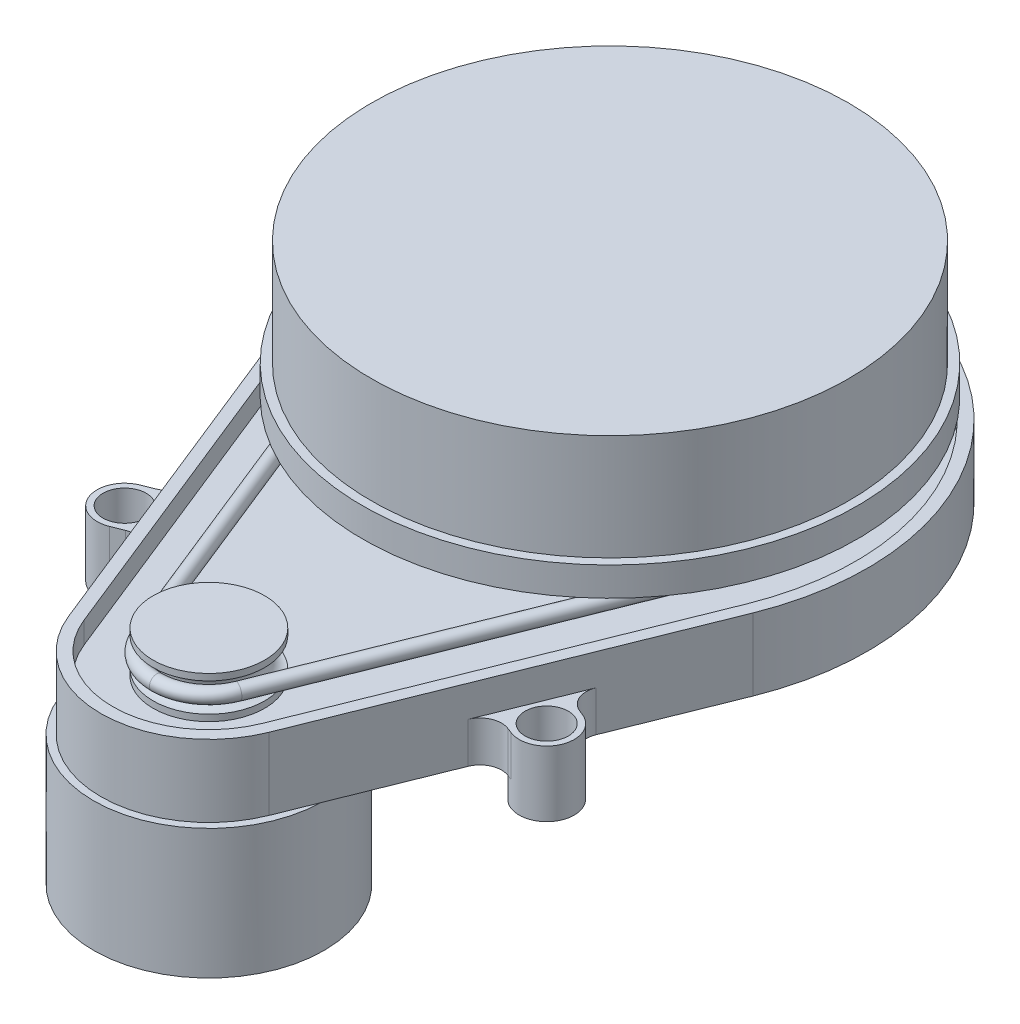
SolidWorks part; units mm, degrees
ref_plane "前基準面" through (0, 0, 0) normal (0, 0, 1) x (1, 0, 0)
ref_plane "上基準面" through (0, 0, 0) normal (0, 1, 0) x (1, 0, 0)
ref_plane "右基準面" through (0, 0, 0) normal (1, 0, 0) x (0, 0, -1)
sketch "草圖1" plane through (0, 0, 0) normal (0, 1, 0) x (1, 0, 0)
  line L0 (0, 0) -> (0, 50000) construction
  line L1 (0, 0) -> (50000, 0) construction
  line L2 (0, 39.9) -> (-5.4, 39.9)
  line L3 (0, -36.6) -> (27.81, -36.6)
  line L4 (0, -39.7) -> (-27.7, -39.7)
  line L5 (33.1767, -13.318) -> (13.9203, -61.288)
  line L6 (-33.1767, -13.318) -> (-13.9203, -61.288)
  circle A0 centre (0, 0) radius 35.75
  circle A1 centre (0, -55.7) radius 15
  point P14 (0, -70.7)
  dimension "D1" = 71.5
  dimension "D9" = 30
  dimension "D2" = 5.4
  dimension "D3" = 39.9
  dimension "D4" = 27.81
  dimension "D5" = 27.7
  dimension "D6" = 76.5
  dimension "D7" = 110.6
  dimension "D8" = 79.6
sketch "草圖2" plane through (0, 0, 0) normal (0, 1, 0) x (1, 0, 0)
  line L0 (-33.1767, -13.318) -> (-13.9203, -61.288) construction
  line L1 (33.1767, -13.318) -> (13.9203, -61.288) construction
  line L2 (-33.1767, -13.318) -> (-13.9203, -61.288)
  line L3 (33.1767, -13.318) -> (13.9203, -61.288)
  circle A0 centre (0, -55.7) radius 15 construction
  circle A1 centre (0, 0) radius 35.75 construction
  arc A2 (-13.9203, -61.288) -> (13.9203, -61.288) centre (0, -55.7) ccw
  arc A3 (33.1767, -13.318) -> (-33.1767, -13.318) centre (0, 0) ccw
extrude "填料-伸長1" add sketch "草圖2" along normal blind 10
sketch "草圖3" plane through (0, 10, 0) normal (0, 1, 0) x (1, 0, 0)
  line L22 (12.3891, -60.6733) -> (31.6455, -12.7033)
  line L23 (-31.6455, -12.7033) -> (-12.3891, -60.6733)
  line L24 (-33.1767, -13.318) -> (-13.9203, -61.288)
  line L25 (13.9203, -61.288) -> (33.1767, -13.318)
  line L26 (-33.1767, -13.318) -> (-13.9203, -61.288)
  line L27 (13.9203, -61.288) -> (33.1767, -13.318)
  arc A20 (31.6455, -12.7033) -> (-31.6455, -12.7033) centre (0, 0) ccw
  arc A21 (-12.3891, -60.6733) -> (12.3891, -60.6733) centre (0, -55.7) ccw
  arc A22 (33.1767, -13.318) -> (-33.1767, -13.318) centre (0, 0) ccw
  arc A23 (-13.9203, -61.288) -> (13.9203, -61.288) centre (0, -55.7) ccw
  arc A24 (33.1767, -13.318) -> (-33.1767, -13.318) centre (0, 0) ccw
  arc A25 (-13.9203, -61.288) -> (13.9203, -61.288) centre (0, -55.7) ccw
  dimension "D1" = 0
  dimension "D2" = 1.65
extrude "除料-伸長1" cut sketch "草圖3" against normal blind 3 contours L23 A21 L22 A20 region at (0, 10, 11.8793)
sketch "草圖4" plane through (0, 7, 0) normal (0, 1, 0) x (1, 0, 0)
  circle A0 centre (0, -55.7) radius 7.75
  dimension "D1" = 15.5
extrude "填料-伸長2" add sketch "草圖4" along normal blind 5.8
sketch "草圖5" plane through (0, 0, 0) normal (1, 0, 0) x (0, 0, -1)
  line L0 (-47.95, 7) -> (-47.95, 12.8) construction
  line L1 (-47.95, 11.9) -> (-47.95, 7.9)
  arc A0 (-47.95, 11.9) -> (-47.95, 7.9) centre (-47.95, 9.9) ccw
  dimension "D1" = 4
revolve "除料-旋轉1" cut sketch "草圖5" angle 360 about axis through (0, 12.8, 55.7) along (0, -1, 0)
sketch "草圖6" plane through (0, 0, 0) normal (1, 0, 0) x (0, 0, -1)
  line L0 (0, 10) -> (0, 0) construction
  line L1 (10, 12.8) -> (34.35, 12.8)
  line L2 (0, 7) -> (0, 31.5)
  line L3 (0, 31.5) -> (33.15, 31.5)
  line L4 (34.35, 12.8) -> (34.35, 16.8)
  line L6 (10, 12.8) -> (10, 7)
  line L7 (10, 7) -> (0, 7)
  line L9 (34.1, 7) -> (-12.7033, 7) construction
  line L10 (-47.95, 12.8) -> (-63.45, 12.8) construction
  line L14 (34.35, 16.8) -> (33.15, 16.8)
  line L15 (33.15, 31.5) -> (33.15, 16.8)
  dimension "D1" = 10
  dimension "D2" = 18.7
  dimension "D3" = 34.35
  dimension "D4" = 33.15
  dimension "D5" = 4
revolve "旋轉1" add sketch "草圖6" angle 360 about L2
ref_plane "平面1" through (0, 9.9, 0) normal (0, 1, 0) x (1, 0, 0)
sketch "草圖7" plane through (0, 9.9, 0) normal (0, 1, 0) x (1, 0, 0)
  line L0 (25.5205, -10.2446) -> (6.2641, -58.2146)
  line L1 (-25.5205, -10.2446) -> (-6.2641, -58.2146)
  line L2 (-31.6455, -12.7033) -> (-12.3891, -60.6733) construction
  line L3 (12.3891, -60.6733) -> (31.6455, -12.7033) construction
  arc A1 (25.5205, -10.2446) -> (-25.5205, -10.2446) centre (0, 0) ccw
  circle A2 centre (0, -55.7) radius 6.75
  arc A3 (-6.2641, -58.2146) -> (6.2641, -58.2146) centre (0, -55.7) ccw
  dimension "D1" = 1
sketch "草圖8" plane through (0, 0, 0) normal (1, 0, 0) x (0, 0, -1)
  line L0 (-63.45, 12.8) -> (-63.45, 7) construction
  line L1 (-63.45, 7.9) -> (-63.45, 7) construction
  line L2 (10, 7) -> (-10, 7) construction
  circle A0 centre (-62.95, 9.9) radius 1
  point P10 (-63.45, 9.9)
  dimension "D2" = 2
  dimension "D1" = 0.5
sweep "掃出1" add profiles "草圖8" path "草圖7"
sketch "草圖9" plane through (0, 0, 0) normal (0, 1, 0) x (1, 0, 0)
  line L0 (33.1767, -13.318) -> (13.9203, -61.288) construction
  line L1 (-33.1767, -13.318) -> (-13.9203, -61.288) construction
  line L2 (33.1767, -13.318) -> (13.9203, -61.288) construction
  line L3 (-33.1767, -13.318) -> (-13.9203, -61.288) construction
  line L4 (33.1767, -13.318) -> (13.9203, -61.288) construction
  line L5 (-33.1767, -13.318) -> (-13.9203, -61.288) construction
  line L6 (0, -39.7) -> (-27.7, -39.7) construction
  line L7 (0, -36.6) -> (27.81, -36.6) construction
  line L8 (0, 39.9) -> (-5.4, 39.9) construction
  line L9 (33.1767, -13.318) -> (13.9203, -61.288) construction
  line L10 (0, -39.7) -> (-27.7, -39.7) construction
  line L11 (0, -36.6) -> (27.81, -36.6) construction
  line L12 (0, 39.9) -> (-5.4, 39.9) construction
  line L13 (-33.1767, -13.318) -> (-13.9203, -61.288) construction
  line L14 (29.2349, -33.0503) -> (25.8079, -31.6746)
  line L15 (26.3851, -40.1497) -> (22.958, -38.774)
  line L16 (-29.1249, -36.1503) -> (-24.7209, -34.3824)
  line L17 (-26.2751, -43.2497) -> (-21.871, -41.4818)
  line L18 (-9.225, 39.9) -> (-9.225, 34.5393)
  line L19 (-1.575, 39.9) -> (-1.575, 35.7153)
  line L20 (-24.7209, -34.3824) -> (-21.871, -41.4818)
  line L21 (25.8079, -31.6746) -> (22.958, -38.774)
  arc A0 (26.3851, -40.1497) -> (29.2349, -33.0503) centre (27.81, -36.6) ccw
  circle A1 centre (0, -55.7) radius 15
  circle A2 centre (0, -55.7) radius 15 construction
  circle A3 centre (0, 0) radius 35.75
  circle A4 centre (0, 0) radius 35.75 construction
  arc A5 (-29.1249, -36.1503) -> (-26.2751, -43.2497) centre (-27.7, -39.7) ccw
  arc A6 (-1.575, 39.9) -> (-9.225, 39.9) centre (-5.4, 39.9) ccw
  arc A7 (-1.575, 35.7153) -> (-9.225, 34.5393) centre (0, 0) ccw
  dimension "D3" = 7.65
  dimension "D1" = 0
  dimension "D2" = 0
extrude "填料-伸長3" add sketch "草圖9" along normal blind 5.65
sketch "草圖10" plane through (0, 0, 0) normal (0, -1, 0) x (1, 0, 0)
  circle A0 centre (27.81, 36.6) radius 3.825
  circle A1 centre (-5.4, -39.9) radius 3.825
  circle A2 centre (-27.7, 39.7) radius 3.825
  arc A3 (-26.2751, 43.2497) -> (-29.1249, 36.1503) centre (-27.7, 39.7) ccw construction
  arc A4 (29.2349, 33.0503) -> (26.3851, 40.1497) centre (27.81, 36.6) ccw construction
  arc A5 (-9.225, -39.9) -> (-1.575, -39.9) centre (-5.4, -39.9) ccw construction
extrude "填料-伸長4" add sketch "草圖10" along normal blind 3.45
sketch "草圖11" plane through (0, 5.65, 0) normal (0, 1, 0) x (1, 0, 0)
  circle A0 centre (-5.4, 39.9) radius 3
  circle A1 centre (27.81, -36.6) radius 3
  circle A2 centre (-27.7, -39.7) radius 3
  dimension "D1" = 6
extrude "除料-伸長2" cut sketch "草圖11" against normal blind 4.85
sketch "草圖12" plane through (0, 0.8, 0) normal (0, 1, 0) x (1, 0, 0)
  circle A0 centre (27.81, -36.6) radius 1.7
  circle A1 centre (-27.7, -39.7) radius 1.7
  circle A2 centre (-5.4, 39.9) radius 1.7
  dimension "D1" = 3.4
extrude "除料-伸長3" cut sketch "草圖12" against normal through all
sketch "草圖13" plane through (0, -3.45, 0) normal (0, -1, 0) x (1, 0, 0)
  circle A1 centre (-27.7, 39.7) radius 3
  circle A2 centre (-27.7, 39.7) radius 3
  circle A3 centre (27.81, 36.6) radius 3
  circle A4 centre (27.81, 36.6) radius 3
  circle A5 centre (-5.4, -39.9) radius 3
  circle A6 centre (-5.4, -39.9) radius 3
  dimension "D1" = 0
  dimension "D2" = 0
  dimension "D3" = 0
extrude "除料-伸長4" cut sketch "草圖13" against normal blind 2
sketch "草圖14" plane through (0, 0, 0) normal (0, -1, 0) x (1, 0, 0)
  circle A0 centre (0, 55.7) radius 16
  dimension "D1" = 32
extrude "填料-伸長5" add sketch "草圖14" along normal blind 18
sketch "草圖15" plane through (0, -18, 0) normal (0, -1, 0) x (1, 0, 0)
  circle A0 centre (0, 55.7) radius 3.75
  dimension "D1" = 7.5
extrude "填料-伸長6" add sketch "草圖15" along normal blind 3
sketch "草圖16" plane through (0, 0, 0) normal (0, 0, 1) x (1, 0, 0)
  line L0 (-33.15, 24.15) -> (33.15, 24.15) construction
  line L1 (-33.15, 31.5) -> (-33.15, 16.8) construction
  line L2 (33.15, 16.8) -> (33.15, 31.5) construction
  line L3 (-13.575, 24.15) -> (-19.575, 24.15) construction
  line L4 (-13.575, 18.9) -> (-19.575, 18.9)
  line L5 (-13.575, 29.4) -> (-19.575, 29.4)
  arc A0 (-13.575, 18.9) -> (-13.575, 29.4) centre (-13.575, 24.15) ccw
  arc A1 (-19.575, 29.4) -> (-19.575, 18.9) centre (-19.575, 24.15) ccw
  circle A2 centre (15, 24.15) radius 5.25
  point P8 (-16.575, 24.15)
  point P13 (-24.825, 24.15)
  point P14 (-8.325, 24.15)
  dimension "D4" = 15
  dimension "D1" = 10.5
  dimension "D2" = 16.5
  dimension "D3" = 16.575
extrude "除料-伸長5" cut sketch "草圖16" against normal through all
fillet "圓角1" radius 3 6 edges at (-1.575, 2.825, -35.7153) (-9.225, 2.825, -34.5393) (-24.7209, 2.825, 34.3824) (-21.871, 2.825, 41.4818) (25.8079, 2.825, 31.6746) (22.958, 2.825, 38.774)
